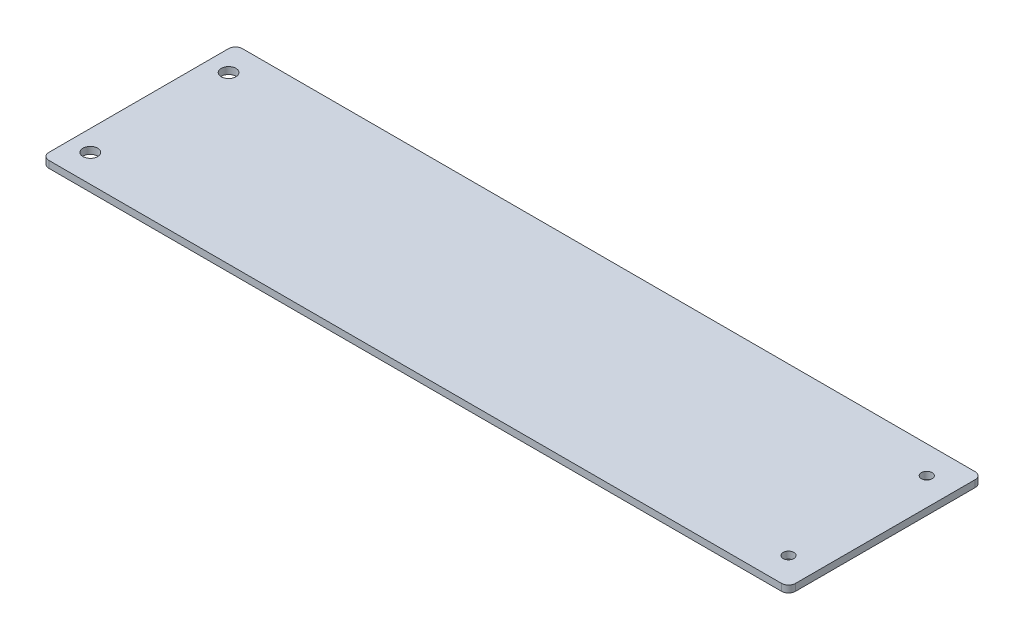
SolidWorks part; units mm, degrees
material "PE High Density"
ref_plane "Front Plane" through (0, 0, 0) normal (0, 0, 1) x (1, 0, 0)
ref_plane "Top Plane" through (0, 0, 0) normal (0, 1, 0) x (1, 0, 0)
ref_plane "Right Plane" through (0, 0, 0) normal (1, 0, 0) x (0, 0, -1)
sketch "Sketch1" plane through (0, 0, 0) normal (0, 1, 0) x (1, 0, 0)
  line L1 (-171.45, -44.45) -> (171.45, -44.45)
  line L2 (-171.45, -44.45) -> (-171.45, 44.45)
  line L3 (-171.45, 44.45) -> (171.45, 44.45)
  line L4 (171.45, -44.45) -> (171.45, 44.45)
  line L5 (-171.45, -44.45) -> (171.45, 44.45) construction
  line L6 (-171.45, 44.45) -> (171.45, -44.45) construction
  point P0 (0, 0)
  dimension "D1" = 342.9
  dimension "D2" = 88.9
extrude "Boss-Extrude1" add sketch "Sketch1" along normal blind 3.175
sketch "Sketch2" plane through (0, 3.175, 0) normal (0, 1, 0) x (1, 0, 0)
  line L0 (-171.45, 44.45) -> (-171.45, -44.45) construction
  line L1 (-161.925, 31.75) -> (158.75, 31.75) construction
  line L2 (-161.925, 31.75) -> (-161.925, -31.75) construction
  line L3 (-161.925, -31.75) -> (158.75, -31.75) construction
  line L4 (158.75, 31.75) -> (158.75, -31.75) construction
  line L5 (-161.925, 31.75) -> (158.75, -31.75) construction
  line L6 (-161.925, -31.75) -> (158.75, 31.75) construction
  line L7 (171.45, -44.45) -> (171.45, 44.45) construction
  line L8 (171.45, 44.45) -> (-171.45, 44.45) construction
  point P0 (-1.5875, 0)
  dimension "D1" = 63.5
  dimension "D2" = 9.525
  dimension "D3" = 12.7
  dimension "D4" = 12.7
hole_wizard "17/64 (0.26563) Diameter Hole1" positions "Sketch3" profile "Sketch4" hole size "17/64" standard "ANSI Inch" end condition through all
sketch "Sketch3" plane through (0, 3.175, 0) normal (0, 1, 0) x (1, 0, 0)
  point P0 (-161.925, 31.75)
  point P3 (-161.925, -31.75)
sketch "Sketch4" plane through (-161.925, 3.175, -31.75) normal (1, 0, 0) x (0, 0, 1)
  line L0 (0, 0) -> (0, 3.175)
  line L1 (0, 3.175) -> (3.3735, 3.175)
  line L2 (3.3735, 3.175) -> (3.3735, 0)
  line L5 (3.3735, 0) -> (0, 0)
  line L11 (0, -6.35) -> (0, 107.95) construction
  dimension "Thru Hole Dia." = 6.747
  dimension "Thru Hole Depth" = 3.175
hole_wizard "#10 (0.1935) Diameter Hole1" positions "Sketch5" profile "Sketch6" hole size "#10" standard "ANSI Inch" end condition through all
sketch "Sketch5" plane through (0, 3.175, 0) normal (0, 1, 0) x (1, 0, 0)
  point P0 (158.75, 31.75)
  point P3 (158.75, -31.75)
sketch "Sketch6" plane through (158.75, 3.175, -31.75) normal (1, 0, 0) x (0, 0, 1)
  line L0 (0, 0) -> (0, 3.175)
  line L1 (0, 3.175) -> (2.4574, 3.175)
  line L2 (2.4574, 3.175) -> (2.4574, 0)
  line L5 (2.4574, 0) -> (0, 0)
  line L11 (0, -6.35) -> (0, 107.95) construction
  dimension "Thru Hole Dia." = 4.9149
  dimension "Thru Hole Depth" = 3.175
fillet "Fillet1" radius 3.175 4 edges at (-171.45, 1.5875, -44.45) (-171.45, 1.5875, 44.45) (171.45, 1.5875, 44.45) (171.45, 1.5875, -44.45)
